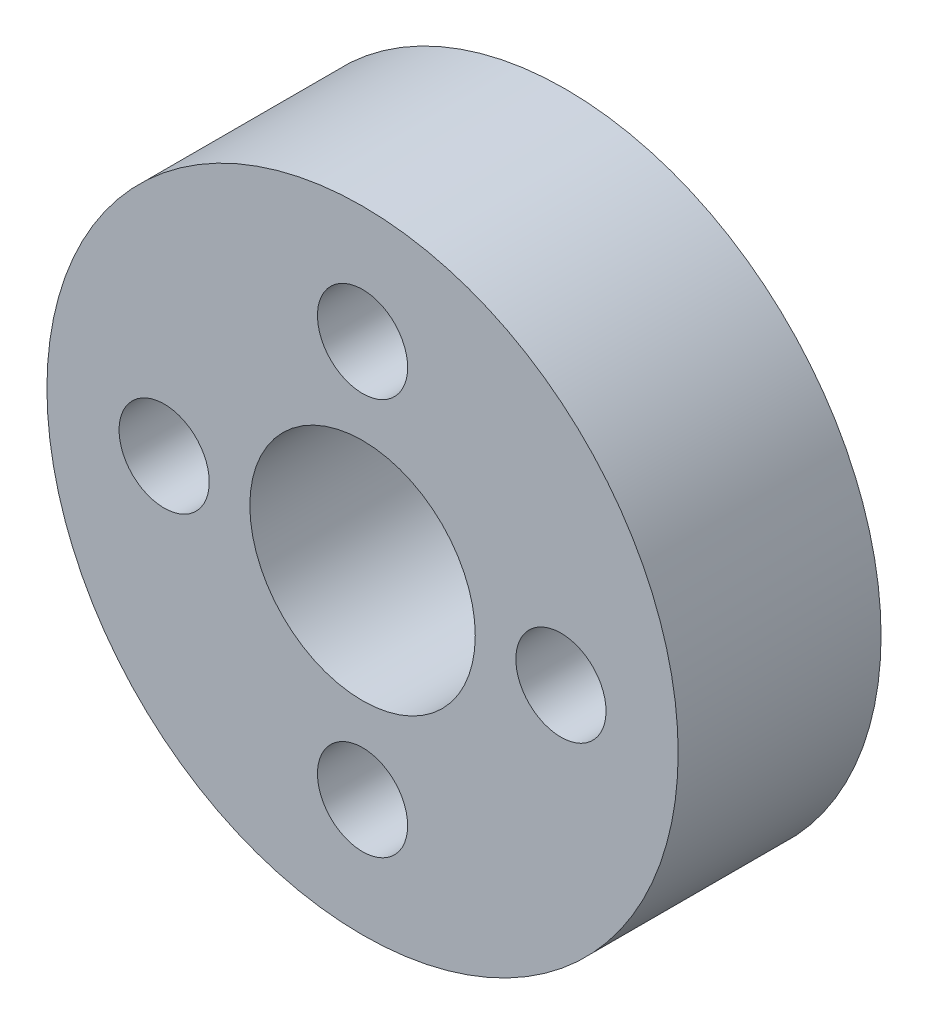
SolidWorks part; units mm, degrees
ref_plane "Front Plane" through (0, 0, 0) normal (0, 0, 1) x (1, 0, 0)
ref_plane "Top Plane" through (0, 0, 0) normal (0, 1, 0) x (1, 0, 0)
ref_plane "Right Plane" through (0, 0, 0) normal (1, 0, 0) x (0, 0, -1)
sketch "Sketch1" plane through (0, 0, 0) normal (0, 0, 1) x (1, 0, 0)
  line L0 (0, 11.176) -> (0, 0) construction
  line L5 (0, 0) -> (11.176, 0) construction
  line L6 (0, -11.176) -> (0, 0) construction
  line L7 (0, 0) -> (-11.176, 0) construction
  circle A0 centre (0, 0) radius 17.78
  circle A1 centre (-11.176, 0) radius 2.54
  circle A2 centre (0, -11.176) radius 2.54
  circle A3 centre (11.176, 0) radius 2.54
  circle A4 centre (0, 11.176) radius 2.54
  circle A5 centre (0, 0) radius 6.35
  dimension "D1" = 35.56
  dimension "D4" = 5.08
  dimension "D2" = 12.7
  dimension "D3" = 11.176
extrude "Boss-Extrude1" add sketch "Sketch1" along normal blind 11.43
sketch "Sketch2" plane through (0, 0, 0) normal (0, 0, -1) x (-1, 0, 0)
  line L1 (-8.255, -8.255) -> (8.255, -8.255)
  line L2 (-8.255, -8.255) -> (-8.255, 8.255)
  line L3 (-8.255, 8.255) -> (8.255, 8.255)
  line L4 (8.255, -8.255) -> (8.255, 8.255)
  line L5 (-8.255, -8.255) -> (8.255, 8.255) construction
  line L6 (-8.255, 8.255) -> (8.255, -8.255) construction
  circle A0 centre (0, 0) radius 6.35 construction
  circle A1 centre (0, 0) radius 6.35
  point P0 (0, 0)
  dimension "D1" = 16.51
extrude "Boss-Extrude2" add sketch "Sketch2" along normal blind 3.175
